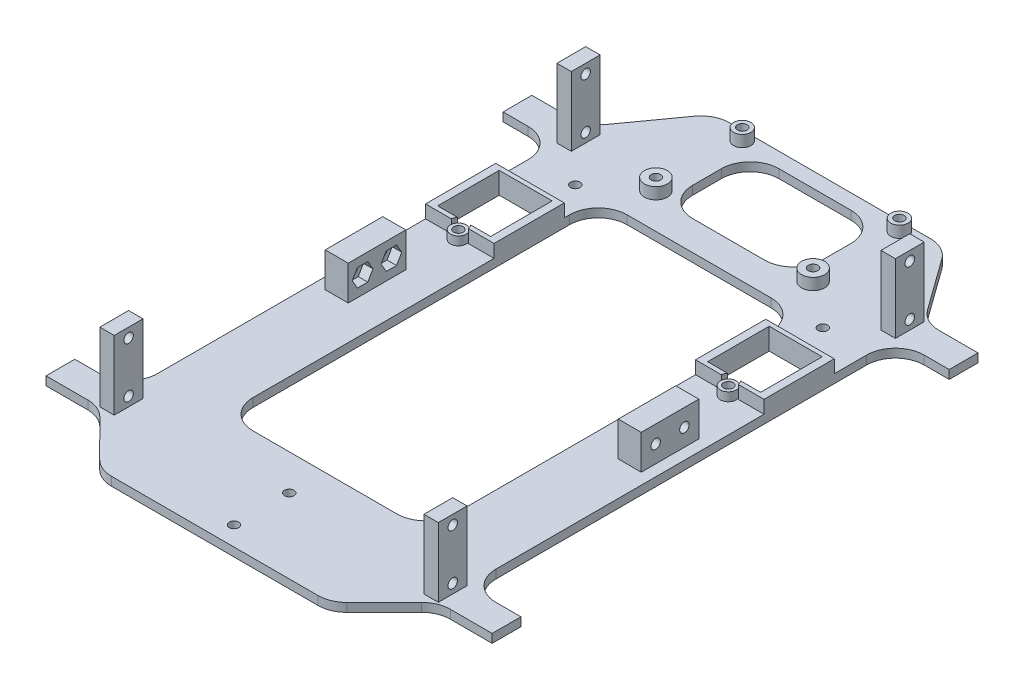
SolidWorks part; units mm, degrees
ref_plane "Front Plane" through (0, 0, 0) normal (0, 0, 1) x (1, 0, 0)
ref_plane "Top Plane" through (0, 0, 0) normal (0, 1, 0) x (1, 0, 0)
ref_plane "Right Plane" through (0, 0, 0) normal (1, 0, 0) x (0, 0, -1)
sketch "Sketch1" plane through (0, 0, 0) normal (0, 1, 0) x (1, 0, 0)
  line L0 (-114.2434, -89.942) -> (-114.2434, -91.942) construction
  line L1 (-149.2434, 40.058) -> (-79.2434, 40.058)
  line L2 (-149.2434, 40.058) -> (-149.2434, -89.942)
  line L3 (-149.2434, -89.942) -> (-79.2434, -89.942)
  line L4 (-79.2434, 40.058) -> (-79.2434, -89.942)
  line L9 (-114.2434, -89.942) -> (-114.2434, -91.942) construction
  line L10 (-151.7434, -91.942) -> (-76.7434, -91.942) construction
  line L11 (-114.2434, -91.942) -> (-151.7434, -91.942) construction
  line L12 (-151.7434, -91.942) -> (-151.7434, -131.942) construction
  line L13 (-114.2434, -91.942) -> (-76.7434, -91.942) construction
  line L14 (-76.7434, -91.942) -> (-76.7434, -131.942) construction
  line L15 (-114.2434, 45.058) -> (-114.2434, 85.558) construction
  line L16 (-114.2434, -131.942) -> (-151.7434, -131.942) construction
  line L17 (-114.2434, -131.942) -> (-76.7434, -131.942) construction
  line L19 (-114.2434, -91.942) -> (-114.2434, -131.942) construction
  line L20 (-151.7434, -111.942) -> (-76.7434, -111.942) construction
  line L22 (-154.2434, 45.058) -> (-74.2434, 45.058) construction
  line L23 (-154.2434, 85.558) -> (-74.2434, 85.558)
  line L25 (-74.2434, 65.308) -> (-154.2434, 65.308) construction
  line L26 (-114.2434, 65.308) -> (-114.2434, 48.258) construction
  line L27 (-114.2434, 65.308) -> (-114.2434, 82.358) construction
  line L28 (-114.2434, 65.308) -> (-86.9434, 65.308) construction
  line L29 (-114.2434, -123.192) -> (-114.2434, -131.1897) construction
  line L32 (-114.2434, 40.058) -> (-114.2434, -89.942) construction
  line L33 (-114.2434, -123.192) -> (-114.2434, -128.192) construction
  line L34 (-154.2434, -128.192) -> (-74.2434, -128.192)
  line L35 (-114.2434, 45.058) -> (-114.2434, 40.058) construction
  line L36 (-114.2434, 65.308) -> (-141.5434, 65.308) construction
  line L37 (-141.5434, 82.358) -> (-86.9434, 82.358) construction
  line L38 (-86.9434, 82.358) -> (-86.9434, 48.258) construction
  line L39 (-86.9434, 48.258) -> (-141.5434, 48.258) construction
  line L40 (-141.5434, 48.258) -> (-141.5434, 82.358) construction
  line L42 (-136.7434, 80.308) -> (-91.7434, 80.308)
  line L43 (-136.7434, 80.308) -> (-136.7434, 50.308)
  line L44 (-136.7434, 50.308) -> (-91.7434, 50.308)
  line L45 (-91.7434, 80.308) -> (-91.7434, 50.308)
  line L46 (-136.7434, 80.308) -> (-91.7434, 50.308) construction
  line L47 (-136.7434, 50.308) -> (-91.7434, 80.308) construction
  line L49 (-114.2434, -24.942) -> (-173.0434, -24.942) construction
  line L50 (-114.2434, -24.942) -> (-55.4434, -24.942) construction
  line L51 (-173.0434, 85.558) -> (-173.0434, 59.458) construction
  line L52 (-173.0434, -128.192) -> (-55.4434, -128.192) construction
  line L53 (-55.4434, -128.192) -> (-55.4434, -109.342) construction
  line L54 (-55.4434, 85.558) -> (-173.0434, 85.558) construction
  line L55 (-173.0434, -24.942) -> (-173.0434, 49.458) construction
  line L56 (-173.0434, 54.458) -> (-55.4434, 54.458) construction
  line L57 (-173.0434, -24.942) -> (-173.0434, -99.342) construction
  line L58 (-173.0434, -104.342) -> (-55.4434, -104.342) construction
  line L60 (-55.4434, -104.342) -> (-55.4434, -99.342) construction
  line L62 (-55.4434, 49.458) -> (-55.4434, -99.342)
  line L63 (-55.4434, -104.342) -> (-55.4434, -99.342)
  line L64 (-149.2434, 40.058) -> (-149.2434, -24.942) construction
  line L65 (-149.2434, 7.558) -> (-149.2434, 40.058) construction
  line L66 (-173.0434, 49.458) -> (-173.0434, -99.342)
  line L67 (-55.4434, 59.458) -> (-55.4434, 85.558) construction
  line L69 (-149.2434, 23.808) -> (-149.2434, 7.558) construction
  line L70 (-173.0434, 15.683) -> (-55.4434, 15.683) construction
  line L71 (-173.0434, -109.342) -> (-173.0434, -128.192) construction
  line L72 (-149.2434, 15.683) -> (-173.0434, 15.683) construction
  line L74 (-55.4434, 15.683) -> (-79.2434, 15.683) construction
  line L75 (-55.4434, 59.458) -> (-74.2434, 85.558)
  line L76 (-154.2434, 85.558) -> (-173.0434, 59.458)
  line L77 (-173.0434, -109.342) -> (-154.2434, -128.192)
  line L78 (-55.4434, -109.342) -> (-74.2434, -128.192)
  line L79 (-173.0434, 15.683) -> (-149.2434, 15.683) construction
  line L80 (-55.4434, 15.683) -> (-79.2434, 15.683) construction
  line L81 (-173.0434, 49.458) -> (-173.0434, -99.342) construction
  line L82 (-173.0434, 59.458) -> (-191.7434, 59.458)
  line L84 (-173.0434, 49.458) -> (-191.7434, 49.458)
  line L85 (-191.7434, 59.458) -> (-191.7434, 49.458)
  line L86 (-55.4434, 59.458) -> (-36.7434, 59.458)
  line L88 (-55.4434, 49.458) -> (-36.7434, 49.458)
  line L89 (-36.7434, 59.458) -> (-36.7434, 49.458)
  line L90 (-55.4434, -99.342) -> (-36.7434, -99.342)
  line L91 (-55.4434, -99.342) -> (-55.4434, -104.342)
  line L92 (-55.4434, -109.342) -> (-36.7434, -109.342)
  line L93 (-36.7434, -99.342) -> (-36.7434, -109.342)
  line L94 (-173.0434, -99.342) -> (-191.7434, -99.342)
  line L96 (-173.0434, -109.342) -> (-191.7434, -109.342)
  line L97 (-191.7434, -99.342) -> (-191.7434, -109.342)
  line L99 (-173.0434, 15.683) -> (-149.2434, 15.683) construction
  line L100 (-149.2434, 40.058) -> (-157.2434, 40.058) construction
  line L101 (-79.2434, 40.058) -> (-71.2434, 40.058) construction
  line L102 (-55.4434, 15.683) -> (-79.2434, 15.683) construction
  line L103 (-141.5434, 82.358) -> (-141.5434, 52.358) construction
  line L104 (-141.5434, 52.358) -> (-86.9434, 52.358) construction
  line L106 (-151.9434, 26.7212) -> (-170.3434, 26.7212)
  line L107 (-151.9434, 26.7212) -> (-151.9434, 5.3212)
  line L108 (-151.9434, 5.3212) -> (-170.3434, 5.3212)
  line L109 (-170.3434, 26.7212) -> (-170.3434, 5.3212)
  line L110 (-151.9434, 26.7212) -> (-170.3434, 5.3212) construction
  line L111 (-151.9434, 5.3212) -> (-170.3434, 26.7212) construction
  line L112 (-58.1434, 26.7212) -> (-76.5434, 26.7212)
  line L113 (-58.1434, 26.7212) -> (-58.1434, 5.3212)
  line L114 (-58.1434, 5.3212) -> (-76.5434, 5.3212)
  line L115 (-76.5434, 26.7212) -> (-76.5434, 5.3212)
  line L116 (-58.1434, 26.7212) -> (-76.5434, 5.3212) construction
  line L117 (-58.1434, 5.3212) -> (-76.5434, 26.7212) construction
  circle A0 centre (-114.2434, -121.542) radius 1.65
  circle A1 centre (-114.2434, -102.342) radius 1.65
  circle A6 centre (-141.5434, 82.358) radius 1.65
  circle A7 centre (-86.9434, 82.358) radius 1.65
  circle A10 centre (-157.2434, 40.058) radius 1.65
  circle A11 centre (-71.2434, 40.058) radius 1.65
  circle A12 centre (-141.5434, 52.358) radius 1.65
  circle A13 centre (-86.9434, 52.358) radius 1.65
  dimension "D7" = 45
  dimension "D9" = 9.6
  dimension "D10" = 9.6
  dimension "D11" = 58.8
  dimension "D12" = 58.8
  dimension "D13" = 79.4
  dimension "D14" = 18.7
  dimension "D15" = 18.7
  dimension "D16" = 18.7
  dimension "D17" = 18.7
  dimension "D18" = 21.4
  dimension "D6" = 30
  dimension "D23" = 86
  dimension "D1" = 130
  dimension "D2" = 70
  dimension "D3" = 10
  dimension "D4" = 18.4
  dimension "D5" = 40.5
  dimension "D8" = 2
  dimension "D19" = 21.4
  dimension "D20" = 18.4
  dimension "D21" = 2.7
  dimension "D22" = 2.7
extrude "Boss-Extrude1" add sketch "Sketch1" along normal blind 3 contours L34 A7 A1 A0 L1 L4 L3 L2 region at (-114.2434, 0, -82.9177)
sketch "Sketch3" plane through (0, 3, 0) normal (0, 1, 0) x (1, 0, 0)
  line L5 (-55.4434, 49.458) -> (-60.4434, 49.458)
  line L6 (-55.4434, 49.458) -> (-55.4434, 59.458)
  line L7 (-55.4434, 59.458) -> (-60.4434, 59.458)
  line L8 (-60.4434, 49.458) -> (-60.4434, 59.458)
  line L9 (-173.0434, -99.342) -> (-168.0434, -99.342)
  line L10 (-173.0434, -99.342) -> (-173.0434, -109.342)
  line L11 (-173.0434, -109.342) -> (-168.0434, -109.342)
  line L12 (-168.0434, -99.342) -> (-168.0434, -109.342)
  line L13 (-55.4434, -99.342) -> (-60.4434, -99.342)
  line L14 (-55.4434, -99.342) -> (-55.4434, -109.342)
  line L15 (-55.4434, -109.342) -> (-60.4434, -109.342)
  line L16 (-60.4434, -99.342) -> (-60.4434, -109.342)
  line L17 (-173.0434, 49.458) -> (-168.0434, 49.458)
  line L18 (-173.0434, 49.458) -> (-173.0434, 59.458)
  line L19 (-173.0434, 59.458) -> (-168.0434, 59.458)
  line L20 (-168.0434, 49.458) -> (-168.0434, 59.458)
  dimension "D1" = 5
  dimension "D2" = 5
  dimension "D3" = 5
  dimension "D4" = 5
extrude "Boss-Extrude2" add sketch "Sketch3" along normal blind 24
sketch "Sketch4" plane through (-168.0434, 0, 0) normal (1, 0, 0) x (0, 0, -1)
  line L0 (54.458, 27) -> (54.458, 3) construction
  line L1 (49.458, 27) -> (59.458, 27) construction
  line L2 (49.458, 3) -> (59.458, 3) construction
  line L3 (54.458, 15) -> (54.458, 23.75) construction
  line L4 (54.458, 15) -> (54.458, 6.25) construction
  line L5 (-104.342, 27) -> (-104.342, 3) construction
  line L6 (-109.342, 27) -> (-99.342, 27) construction
  line L7 (-109.342, 3) -> (-99.342, 3) construction
  line L8 (-104.342, 15) -> (-104.342, 23.75) construction
  line L9 (-104.342, 15) -> (-104.342, 6.25) construction
  circle A0 centre (-104.342, 23.75) radius 1.65
  circle A1 centre (-104.342, 6.25) radius 1.65
  circle A2 centre (54.458, 23.75) radius 1.65
  circle A3 centre (54.458, 6.25) radius 1.65
  dimension "D1" = 12
  dimension "D2" = 8.75
  dimension "D3" = 8.75
  dimension "D4" = 12
  dimension "D5" = 8.75
  dimension "D6" = 8.75
extrude "Cut-Extrude1" cut sketch "Sketch4" against normal through all both and the other way through all
sketch "Sketch13" plane through (-173.0434, 0, 0) normal (-1, 0, 0) x (0, 0, 1)
  line L0 (-54.458, 23.75) -> (-44.458, 23.75) construction
  line L1 (-44.458, 23.75) -> (-44.458, 3) construction
  line L2 (-59.458, 3) -> (-49.458, 3) construction
  line L3 (-54.458, 6.25) -> (-44.458, 6.25) construction
  line L4 (104.342, 23.75) -> (94.342, 23.75) construction
  line L5 (104.342, 6.25) -> (94.342, 6.25) construction
  line L6 (94.342, 23.75) -> (94.342, 6.25) construction
  circle A0 centre (-44.458, 23.75) radius 1.65
  circle A1 centre (-44.458, 6.25) radius 1.65
  circle A2 centre (94.342, 23.75) radius 1.65
  circle A3 centre (94.342, 6.25) radius 1.65
fillet "Fillet1" radius 10 20 edges at (-91.7434, 1.5, -50.308) (-136.7434, 1.5, -50.308) (-136.7434, 1.5, -80.308) (-91.7434, 1.5, -80.308) (-74.2434, 1.5, -85.558) (-154.2434, 1.5, -85.558) (-154.2434, 1.5, 128.192) (-74.2434, 1.5, 128.192) (-55.4434, 1.5, 109.342) (-173.0434, 1.5, 109.342) (-173.0434, 1.5, 99.342) (-55.4434, 1.5, -59.458) (-55.4434, 1.5, -49.458) (-55.4434, 1.5, 99.342) (-79.2434, 1.5, 89.942) (-149.2434, 1.5, 89.942) (-149.2434, 1.5, -40.058) (-79.2434, 1.5, -40.058) (-173.0434, 1.5, -59.458) (-173.0434, 1.5, -49.458)
sketch "Sketch5" plane through (0, 3, 0) normal (0, 1, 0) x (1, 0, 0)
  line L0 (-114.2434, 40.058) -> (-114.2434, -89.942) construction
  line L3 (-139.2434, 40.058) -> (-89.2434, 40.058) construction
  line L4 (-139.2434, -89.942) -> (-89.2434, -89.942) construction
  line L10 (-114.2434, -24.942) -> (-149.2434, -24.942) construction
  line L15 (-149.2434, 30.058) -> (-149.2434, -79.942) construction
  line L18 (-114.2434, -24.942) -> (-79.2434, -24.942) construction
  line L19 (-79.2434, 30.058) -> (-79.2434, -79.942) construction
  line L20 (-149.2434, -24.942) -> (-173.0434, -24.942) construction
  line L21 (-173.0434, 39.458) -> (-173.0434, -89.342) construction
  line L22 (-79.2434, -24.942) -> (-55.4434, -24.942) construction
  line L23 (-55.4434, 39.458) -> (-55.4434, -89.342) construction
  line L24 (-161.1434, -24.942) -> (-173.0434, -24.942) construction
  line L25 (-67.3434, -24.942) -> (-55.4434, -24.942) construction
  line L26 (-161.1434, -24.942) -> (-161.1434, -14.942) construction
  line L27 (-161.1434, -24.942) -> (-161.1434, -34.942) construction
  line L28 (-67.3434, -24.942) -> (-67.3434, -14.942) construction
  line L29 (-67.3434, -24.942) -> (-67.3434, -34.942) construction
  line L31 (-161.1434, -14.942) -> (-169.1434, -14.942)
  line L32 (-161.1434, -14.942) -> (-161.1434, -34.942)
  line L33 (-161.1434, -34.942) -> (-169.1434, -34.942)
  line L34 (-169.1434, -14.942) -> (-169.1434, -34.942)
  line L35 (-67.3434, -14.942) -> (-59.3434, -14.942)
  line L36 (-67.3434, -14.942) -> (-67.3434, -34.942)
  line L37 (-67.3434, -34.942) -> (-59.3434, -34.942)
  line L38 (-59.3434, -14.942) -> (-59.3434, -34.942)
  dimension "D1" = 8
  dimension "D2" = 8
extrude "Boss-Extrude3" add sketch "Sketch5" along normal blind 12
sketch "Sketch6" plane through (-161.1434, 0, 0) normal (1, 0, 0) x (0, 0, -1)
  line L0 (-34.942, 9) -> (-14.942, 9) construction
  line L1 (-34.942, 15) -> (-34.942, 3) construction
  line L2 (-14.942, 15) -> (-14.942, 3) construction
  line L3 (-24.942, 9) -> (-14.942, 9) construction
  circle A0 centre (-29.942, 9) radius 1.65
  circle A1 centre (-19.942, 9) radius 1.65
  point P10 (-24.942, 9)
  dimension "D1" = 5
  dimension "D2" = 5
extrude "Cut-Extrude2" cut sketch "Sketch6" against normal through all both and the other way through all
sketch "Sketch7" plane through (-161.1434, 0, 0) normal (1, 0, 0) x (0, 0, -1)
  line L25 (-26.3624, 9) -> (-28.1522, 12.1)
  line L26 (-28.1522, 12.1) -> (-31.7318, 12.1)
  line L27 (-31.7318, 12.1) -> (-33.5216, 9)
  line L28 (-33.5216, 9) -> (-31.7318, 5.9)
  line L29 (-31.7318, 5.9) -> (-28.1522, 5.9)
  line L30 (-28.1522, 5.9) -> (-26.3624, 9)
  line L31 (-16.3624, 9) -> (-18.1522, 12.1)
  line L32 (-18.1522, 12.1) -> (-21.7318, 12.1)
  line L33 (-21.7318, 12.1) -> (-23.5216, 9)
  line L34 (-23.5216, 9) -> (-21.7318, 5.9)
  line L35 (-21.7318, 5.9) -> (-18.1522, 5.9)
  line L36 (-18.1522, 5.9) -> (-16.3624, 9)
  circle A0 centre (-29.942, 9) radius 3.1 construction
  circle A1 centre (-19.942, 9) radius 3.1 construction
extrude "Cut-Extrude3" cut sketch "Sketch7" against normal blind 3.3
sketch "Sketch8" plane through (-67.3434, 0, 0) normal (-1, 0, 0) x (0, 0, 1)
  line L13 (23.5216, 9) -> (21.7318, 12.1)
  line L14 (21.7318, 12.1) -> (18.1522, 12.1)
  line L15 (18.1522, 12.1) -> (16.3624, 9)
  line L16 (16.3624, 9) -> (18.1522, 5.9)
  line L17 (18.1522, 5.9) -> (21.7318, 5.9)
  line L18 (21.7318, 5.9) -> (23.5216, 9)
  line L19 (26.3624, 9) -> (28.1522, 5.9)
  line L20 (28.1522, 5.9) -> (31.7318, 5.9)
  line L21 (31.7318, 5.9) -> (33.5216, 9)
  line L22 (33.5216, 9) -> (31.7318, 12.1)
  line L23 (31.7318, 12.1) -> (28.1522, 12.1)
  line L24 (28.1522, 12.1) -> (26.3624, 9)
  circle A0 centre (19.942, 9) radius 3.1 construction
  circle A1 centre (29.942, 9) radius 3.1 construction
extrude "Cut-Extrude4" cut sketch "Sketch8" against normal blind 3.3
sketch "Sketch9" plane through (0, 3, 0) normal (0, 1, 0) x (1, 0, 0)
  line L0 (-161.1434, 5.3212) -> (-161.1434, 1.3212) construction
  line L4 (-151.9434, 5.3212) -> (-170.3434, 5.3212) construction
  line L5 (-67.3434, 5.3212) -> (-67.3434, 3.3212) construction
  line L6 (-58.1434, 5.3212) -> (-76.5434, 5.3212) construction
  circle A3 centre (-161.1434, 3.3212) radius 2.75
  circle A4 centre (-67.3434, 3.3212) radius 2.75
extrude "Boss-Extrude4" add sketch "Sketch9" along normal blind 3 and the other way up to surface (3 mm away) other way up to face at (-114.2434, 0, 24.0357)
sketch "Sketch10" plane through (0, 6, 0) normal (0, 1, 0) x (1, 0, 0)
  circle A0 centre (-161.1434, 3.3212) radius 1.65
  circle A1 centre (-67.3434, 3.3212) radius 1.65
  dimension "D1" = 3.3
extrude "Cut-Extrude5" cut sketch "Sketch10" against normal through all both and the other way through all
sketch "Sketch11" plane through (0, 3, 0) normal (0, 1, 0) x (1, 0, 0)
  line L0 (-173.0434, 39.458) -> (-173.0434, -89.342) construction
  line L1 (-173.0434, 28.2212) -> (-149.2434, 28.2212)
  line L2 (-173.0434, 28.2212) -> (-173.0434, 3.8212)
  line L3 (-173.0434, 3.8212) -> (-164.1014, 3.8212)
  line L4 (-149.2434, 28.2212) -> (-149.2434, 3.8212)
  line L5 (-149.2434, 30.058) -> (-149.2434, -79.942) construction
  line L6 (-79.2434, 30.058) -> (-79.2434, -79.942) construction
  line L7 (-79.2434, 28.2212) -> (-55.4434, 28.2212)
  line L8 (-79.2434, 28.2212) -> (-79.2434, 3.8212)
  line L9 (-79.2434, 3.8212) -> (-70.3014, 3.8212)
  line L10 (-55.4434, 28.2212) -> (-55.4434, 3.8212)
  line L11 (-55.4434, 39.458) -> (-55.4434, -89.342) construction
  line L12 (-151.9434, 26.7212) -> (-170.3434, 26.7212) construction
  line L13 (-163.0309, 5.3212) -> (-170.3434, 5.3212) construction
  line L14 (-69.2309, 5.3212) -> (-76.5434, 5.3212) construction
  line L15 (-58.1434, 26.7212) -> (-76.5434, 26.7212) construction
  line L16 (-158.1854, 3.8212) -> (-149.2434, 3.8212)
  line L17 (-64.3854, 3.8212) -> (-55.4434, 3.8212)
  line L18 (-58.1434, 5.3212) -> (-65.4559, 5.3212) construction
  line L19 (-170.3434, 26.7212) -> (-151.9434, 26.7212)
  line L20 (-170.3434, 26.7212) -> (-170.3434, 5.3212)
  line L21 (-170.3434, 5.3212) -> (-163.3795, 5.3212)
  line L22 (-151.9434, 26.7212) -> (-151.9434, 5.3212)
  line L23 (-76.5434, 26.7212) -> (-58.1434, 26.7212)
  line L24 (-76.5434, 26.7212) -> (-76.5434, 5.3212)
  line L25 (-76.5434, 5.3212) -> (-69.5795, 5.3212)
  line L26 (-58.1434, 26.7212) -> (-58.1434, 5.3212)
  line L27 (-158.9073, 5.3212) -> (-151.9434, 5.3212)
  line L28 (-65.1073, 5.3212) -> (-58.1434, 5.3212)
  arc A4 (-64.3854, 3.8212) -> (-70.3014, 3.8212) centre (-67.3434, 3.3212) ccw
  arc A5 (-158.1854, 3.8212) -> (-164.1014, 3.8212) centre (-161.1434, 3.3212) ccw
  dimension "D1" = 1.5
  dimension "D2" = 1.5
  dimension "D3" = 1.5
  dimension "D4" = 1.5
extrude "Boss-Extrude6" add sketch "Sketch11" along normal blind 4.5 contours A5 L16 L4 L1 L2 L3 L21 L20 L19 L22 L27 | A4 L17 L10 L7 L8 L9 L25 L24 L23 L26 L28 region at (-161.1434, 3, -27.8804) region at (-67.3434, 3, -27.8804)
sketch "Sketch14" plane through (0, 3, 0) normal (0, 1, 0) x (1, 0, 0)
  circle A0 centre (-141.5434, 52.358) radius 4
  circle A1 centre (-141.5434, 82.358) radius 3
  circle A2 centre (-86.9434, 82.358) radius 3
  circle A3 centre (-86.9434, 52.358) radius 4
  circle A4 centre (-141.5434, 52.358) radius 1.65
  circle A5 centre (-141.5434, 82.358) radius 1.65
  circle A6 centre (-86.9434, 82.358) radius 1.65
  circle A7 centre (-86.9434, 52.358) radius 1.65
extrude "Boss-Extrude7" add sketch "Sketch14" along normal blind 4
